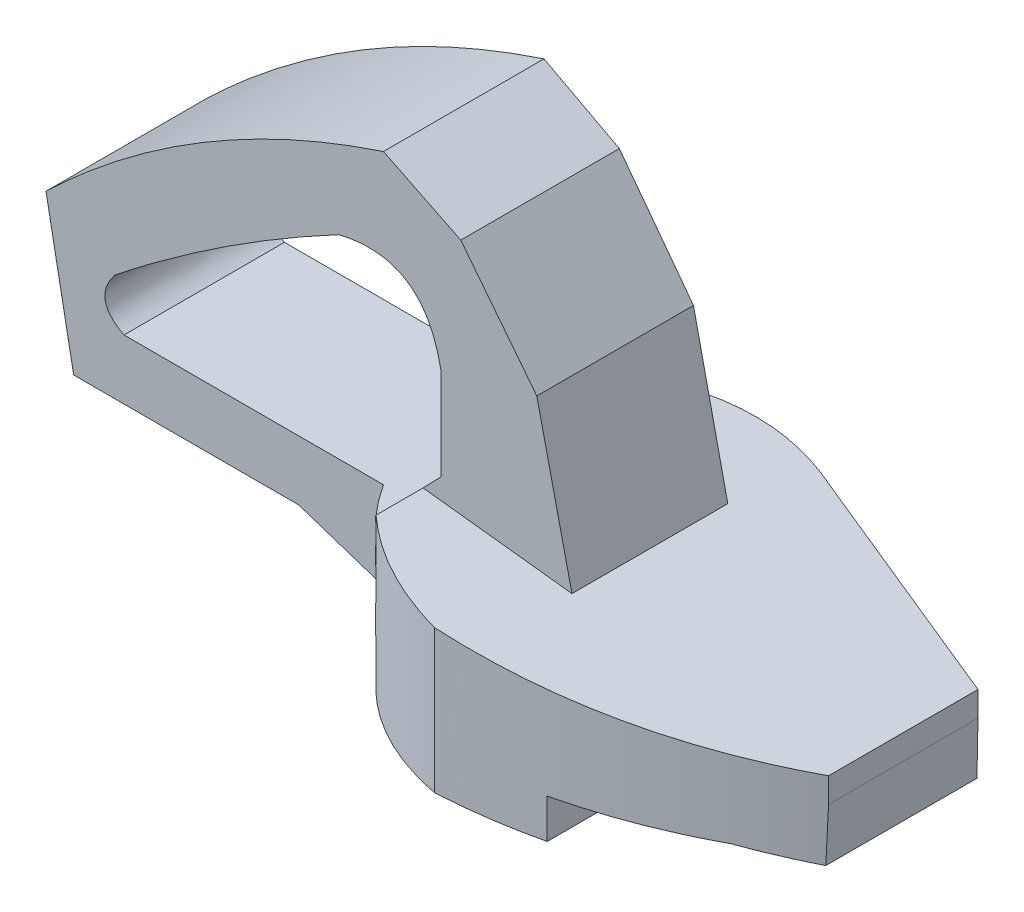
SolidWorks part; units mm, degrees
ref_plane "Front Plane" through (0, 0, 0) normal (0, 0, 1) x (1, 0, 0)
ref_plane "Top Plane" through (0, 0, 0) normal (0, 1, 0) x (1, 0, 0)
ref_plane "Right Plane" through (0, 0, 0) normal (1, 0, 0) x (0, 0, -1)
sketch "Sketch1" plane through (0, 0, 0) normal (0, 1, 0) x (1, 0, 0)
  line L1 (-396.1458, 118.3281) -> (403.8542, 118.3281)
  line L2 (-396.1458, 118.3281) -> (-396.1458, -41.6719)
  line L3 (-396.1458, -41.6719) -> (403.8542, -41.6719)
  line L4 (403.8542, 118.3281) -> (403.8542, -41.6719)
  dimension "D1" = 800
  dimension "D2" = 160
extrude "Boss-Extrude1" add sketch "Sketch1" along normal blind 200
sketch "Sketch2" plane through (0, 0, 41.6719) normal (0, 0, 1) x (1, 0, 0)
  line L0 (-376.1458, 0) -> (-396.1458, 105)
  line L1 (-396.1458, 0) -> (403.8542, 0) construction
  line L2 (-396.1458, 200) -> (-396.1458, 0) construction
  line L3 (-396.1458, 200) -> (403.8542, 200) construction
  line L4 (-238.298, 200) -> (-202.1532, 182.1914)
  line L5 (-202.1532, 182.1914) -> (-166.597, 136.8428)
  line L6 (-166.597, 136.8428) -> (-150.1458, 65)
  line L7 (-150.1458, 65) -> (-30.1458, 51.2241)
  line L8 (-30.1458, 51.2241) -> (403.8542, 25.4)
  line L9 (-376.1458, 0) -> (403.8542, 0)
  line L10 (403.8542, 0) -> (403.8542, 25.4)
  line L12 (-211.517, 125.2834) -> (-211.517, 81.5823)
  line L13 (-359.671, 65) -> (-227.4773, 65)
  line L14 (-227.4773, 65) -> (-211.517, 81.5823)
  line L15 (403.8542, 200) -> (403.8542, 0) construction
  spline S0 degree 2 poles (-396.1458, 105) (-328.422, 170.314) (-238.298, 200) knots 0 0 0 1 1 1
  spline S1 degree 2 poles (-363.8951, 87.1766) (-314.7154, 126.328) (-259.1426, 155.8956) knots 0 0 0 1 1 1
  spline S2 degree 2 poles (-359.671, 65) (-375.1207, 73.2396) (-363.8951, 87.1766) knots 0 0 0 1 1 1
  spline S3 degree 2 poles (-259.1426, 155.8956) (-219.4581, 165.3812) (-211.517, 125.2834) knots 0 0 0 1 1 1
  dimension "D1" = 20
  dimension "D3" = 366
  dimension "D4" = 120
  dimension "D5" = 65
  dimension "D6" = 65
extrude "Cut-Extrude1" cut sketch "Sketch2" against normal blind 210 flip side to cut
sketch "Sketch4" plane through (0, 0, 41.6719) normal (0, 0, 1) x (1, 0, 0)
  line L0 (-383.1966, 37.0167) -> (-277.9563, 37.0167)
  line L1 (-396.1458, 105) -> (-376.1458, 0) construction
  line L2 (-277.9563, 37.0167) -> (-221.5991, 18.4037)
  line L3 (-221.5991, 18.4037) -> (-221.5991, 0)
  line L4 (-376.1458, 0) -> (403.8542, 0) construction
  line L5 (-221.5991, 0) -> (-120.5448, 0)
  line L6 (-120.5448, 0) -> (-120.5448, 18.4037)
  line L7 (-120.5448, 18.4037) -> (-58.3781, 18.4037)
  line L8 (-30.1458, 51.2241) -> (-30.9064, 40.0685)
  line L9 (-30.1458, 51.2241) -> (-150.1458, 65)
  line L10 (-150.1458, 65) -> (-164.1112, 213.0235)
  line L11 (-164.1112, 213.0235) -> (-387.5631, 204.724)
  line L12 (-387.5631, 204.724) -> (-428.0986, 90.1096)
  line L13 (-428.0986, 90.1096) -> (-383.1966, 37.0167)
  line L14 (-30.9064, 40.0685) -> (-30.9064, 0)
  line L15 (-30.9064, 0) -> (-376.1458, 0)
  line L16 (-376.1458, 0) -> (-383.1966, 37.0167)
  line L17 (-58.3781, 18.4037) -> (-30.9064, 14.7249)
  spline S0 degree 2 poles (-58.3781, 18.4037) (-54.94, 39.3184) (-30.9064, 40.0685) knots 0 0 0 1 1 1
  line M20 (-396.1458, 105) -> (-376.1458, 0)
  line M21 (-376.1458, 0) -> (403.8542, 0)
extrude "Cut-Extrude2" cut sketch "Sketch4" against normal blind 210 contours L3 L2 L0 M20 M21 | S0 L7 L6 L14 M21 region at (-306.5819, 17.448, 41.6719) region at (-76.8525, 8.9498, 41.6719)
sketch "Sketch5" plane through (0, 0, 41.6719) normal (0, 0, 1) x (1, 0, 0)
  line L0 (-30.9064, 14.7249) -> (403.8542, 0)
  line L1 (403.8542, 0) -> (-30.9064, 0)
  line L2 (-30.9064, 0) -> (-30.9064, 14.7249)
extrude "Cut-Extrude3" cut sketch "Sketch5" against normal blind 210
sketch "Sketch6" plane through (0, 0, 41.6719) normal (0, 0, 1) x (1, 0, 0)
  line L0 (-30.1458, 51.2241) -> (-30.1458, 39.6107)
  line L1 (-30.1458, 51.2241) -> (418.774, 57.4116)
  line L2 (418.774, 57.4116) -> (439.1818, -10.9868)
  line L3 (439.1818, -10.9868) -> (-58.3781, -23.7866)
  line L4 (-58.3781, -23.7866) -> (-58.3781, 18.4037)
  spline S0 degree 2 poles (-30.1458, 39.6107) (-55.1258, 42.9342) (-58.3781, 18.4037) knots 0 0 0 1 1 1
ref_plane "Plane5" through (0, 200, 0) normal (0, 1, 0) x (1, 0, 0)
sketch "Sketch18" plane through (0, 0, 41.6719) normal (0, 0, 1) x (1, 0, 0)
  line L0 (-30.1458, 39.6107) -> (-30.9064, 14.7249)
  line L1 (-30.1458, 39.6107) -> (-30.1458, 67.9167)
  line L2 (-30.1458, 67.9167) -> (545.595, 67.9167)
  line L3 (545.595, 67.9167) -> (428.9206, -48.7577)
  line L4 (428.9206, -48.7577) -> (-30.9064, 14.7249)
extrude "Cut-Extrude14" cut sketch "Sketch18" against normal blind 180.8
ref_plane "Plane6" through (0, 182.1914, 0) normal (0, 1, 0) x (1, 0, 0)
sketch "Sketch19" plane through (0, 182.1914, 0) normal (0, 1, 0) x (1, 0, 0)
  line L1 (-238.298, 118.3281) -> (-238.298, -41.6719) construction
  line L2 (-30.1458, 118.3281) -> (-30.1458, -41.6719) construction
  line L3 (-238.298, 6.1281) -> (-30.1458, 6.1281)
  line L4 (-238.298, 6.1281) -> (-396.1458, 6.1281)
  line L5 (-396.1458, 118.3281) -> (-396.1458, -41.6719) construction
  line L6 (-396.1458, 6.1281) -> (-396.1458, -41.6719)
  line L7 (-396.1458, -41.6719) -> (-30.1458, -41.6719)
  line L8 (-30.1458, -41.6719) -> (-30.1458, 6.1281)
  spline S1 degree 2 poles (-238.298, 6.1281) (-213.192, -32.6483) (-166.597, -41.6719) knots 0 0 0 1 1 1
  spline S2 degree 2 poles (-166.597, -41.6719) (-91.1304, -37.3258) (-30.1458, 6.1281) knots 0 0 0 1 1 1
  dimension "D1" = 47.8
extrude "Cut-Extrude16" cut sketch "Sketch19" against normal blind 190.8 and the other way blind 180.8 contours S1 L4 L6 L7 | S2 L7 L8 region at (-303.8367, 182.1914, 19.1559) region at (-66.1477, 182.1914, 27.5446)
sketch "Sketch20" plane through (0, 182.1914, 0) normal (0, 1, 0) x (1, 0, 0)
  line L0 (-30.1458, 76.0281) -> (-134.2851, 111.6164)
  line L1 (-30.1458, 118.3281) -> (-30.1458, 6.1281) construction
  line L2 (-166.597, 118.3281) -> (-202.1532, 118.3281) construction
  line L3 (-238.298, 118.3281) -> (-238.298, 6.1281) construction
  line L4 (-238.298, 81.1838) -> (-30.1458, 76.0281)
  line L5 (-30.1458, 118.3281) -> (-396.1458, 118.3281)
  line L6 (-396.1458, 118.3281) -> (-396.1458, 81.1838)
  line L7 (-396.1458, 118.3281) -> (-396.1458, 6.1281) construction
  line L8 (-396.1458, 81.1838) -> (-238.298, 81.1838)
  line L9 (-30.1458, 118.3281) -> (-30.1458, 76.0281)
  spline S0 degree 2 poles (-134.2851, 111.6164) (-191.4772, 134.1296) (-238.298, 81.1838) knots 0 0 0 1 1 1
  dimension "D1" = 42.3
extrude "Cut-Extrude17" cut sketch "Sketch20" against normal blind 200.8 and the other way blind 180.8 contours S0 L5 L6 L8 | S0 L0 L9 L5 region at (-71.7029, 182.1914, -104.2762) region at (-305.1004, 182.1914, -100.709)
sketch "Sketch21" plane through (0, 182.1914, 0) normal (0, 1, 0) x (1, 0, 0)
  line L0 (-238.298, 81.1838) -> (-30.1458, 76.0281)
  line L1 (-30.1458, 76.0281) -> (-30.1458, 124.8418)
  line L2 (-30.1458, 124.8418) -> (-244.7446, 124.8418)
  line L3 (-244.7446, 124.8418) -> (-238.298, 81.1838)
  line L4 (-238.298, 6.1281) -> (-30.1458, 6.1281)
  line L5 (-30.1458, 6.1281) -> (-30.1458, -32.2972)
  line L6 (-30.1458, -32.2972) -> (-30.1458, -55.4939)
  line L7 (-30.1458, -55.4939) -> (-238.298, -55.4939)
  line L8 (-238.298, -55.4939) -> (-238.298, 6.1281)
extrude "Cut-Extrude18" cut sketch "Sketch21" against normal up to surface and the other way blind 200.8 up to face at (-101.9895, 59.4717, -50.2817)
